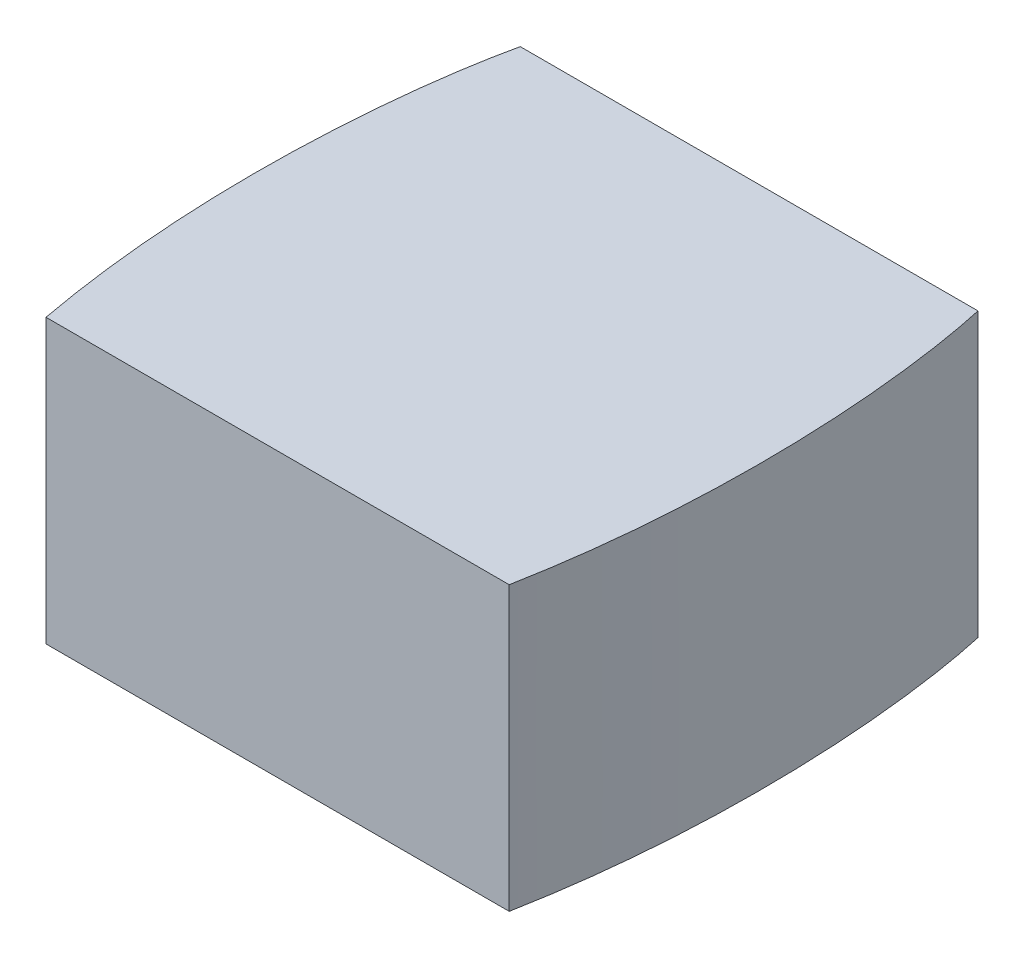
SolidWorks part; units mm, degrees
ref_plane "Front Plane" through (0, 0, 0) normal (0, 0, 1) x (1, 0, 0)
ref_plane "Top Plane" through (0, 0, 0) normal (0, 1, 0) x (1, 0, 0)
ref_plane "Right Plane" through (0, 0, 0) normal (1, 0, 0) x (0, 0, -1)
sketch "Sketch4" plane through (0, 0, 0) normal (0, 0, 1) x (1, 0, 0)
  line L1 (0, 0) -> (60, 0)
  line L2 (0, 0) -> (0, -30)
  line L3 (0, -30) -> (60, -30)
  line L4 (60, 0) -> (60, -30)
  dimension "D1" = 60
  dimension "D2" = 30
extrude "Boss-Extrude3" add sketch "Sketch4" along normal blind 50
sketch "Sketch5" plane through (0, -30, 0) normal (0, -1, 0) x (1, 0, 0)
  line L1 (0, 50) -> (60, 50) construction
  line L2 (54.5605, 50) -> (59.4055, 24.1836) construction
  line L3 (59.4055, 24.1836) -> (55.0652, -1.5289) construction
  line L6 (55.0652, -1.5289) -> (52.1381, -6.6019) construction
  line L7 (30, 50) -> (30, -0.8336)
  line L8 (5.4395, 50) -> (0.5945, 24.1836) construction
  line L9 (0.5945, 24.1836) -> (4.9348, -1.5289) construction
  line L10 (4.9348, -1.5289) -> (7.8619, -6.6019) construction
  line L11 (5.4395, 50) -> (0, 50)
  line L12 (0, 50) -> (0, 0)
  line L13 (0, 0) -> (5.73, 0)
  line L14 (0, 0) -> (60, 0) construction
  line L15 (54.5605, 50) -> (60, 50)
  line L16 (60, 50) -> (60, 0)
  line L17 (60, 0) -> (54.27, 0)
  spline S0 degree 3 poles (54.5605, 50) (59.4055, 24.1836) (55.0652, -1.5289) (52.1381, -6.6019) knots 0 0 0 0 1 1 1 1
  spline S1 degree 3 poles (5.4395, 50) (0.5945, 24.1836) (4.9348, -1.5289) (7.8619, -6.6019) knots 0 0 0 0 1 1 1 1
  line M2 (0, 0) -> (60, 0)
  line M3 (60, 0) -> (60, 50)
  line M4 (60, 50) -> (0, 50)
  line M5 (0, 50) -> (0, 0)
extrude "Cut-Extrude1" cut sketch "Sketch5" against normal blind 50 and the other way through all contours S0 M4 M2 M3 | S1 M4 M5 M2 region at (57.9357, -30, 24.7608) region at (2.0643, -30, 24.7608)
sketch "Sketch6" plane through (0, 0, 0) normal (0, 0, -1) x (-1, 0, 0)
  line L0 (-54.27, -30) -> (-54.27, 0) construction
  line L1 (-5.73, 0) -> (-5.73, -30) construction
  line L2 (-54.27, -27.6033) -> (-58.9495, -27.6033)
  line L3 (-58.9495, -27.6033) -> (-58.9495, -31.6804)
  line L4 (-58.9495, -31.6804) -> (-0.6699, -31.6804)
  line L5 (-54.27, -15) -> (-5.73, -15)
  line L6 (-54.27, -2.3967) -> (-60.7043, -2.3967)
  line L7 (-60.7043, -2.3967) -> (-60.7043, 2.9173)
  line L8 (-60.7043, 2.9173) -> (-0.6699, 2.9173)
  line L9 (-0.6699, 2.9173) -> (-0.6699, -3.5273)
  line L10 (-0.6699, -31.6804) -> (-0.6699, -26.4727)
  spline S0 degree 2 poles (-54.27, -27.6033) (-26.963, -32.1579) (-0.6699, -26.4727) knots 0 0 0 1 1 1
  spline S1 degree 2 poles (-54.27, -2.3967) (-26.963, 2.1579) (-0.6699, -3.5273) knots 0 0 0 1 1 1
